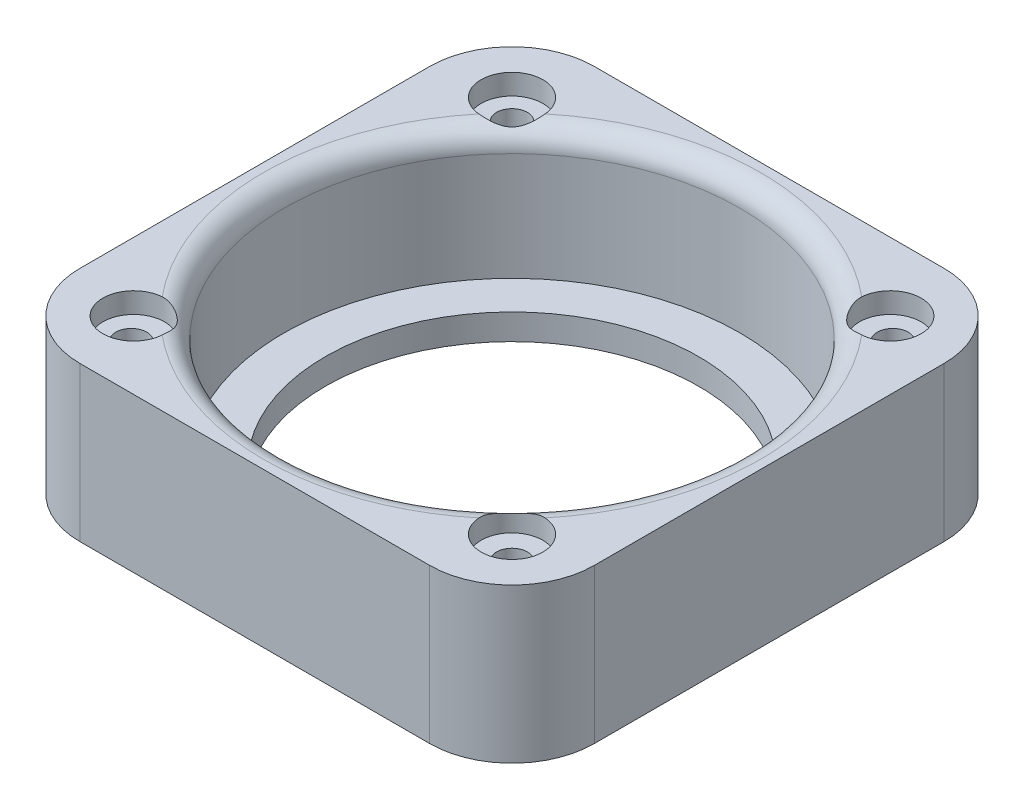
SolidWorks part; units mm, degrees
ref_plane "前视基准面" through (0, 0, 0) normal (0, 0, 1) x (1, 0, 0)
ref_plane "上视基准面" through (0, 0, 0) normal (0, 1, 0) x (1, 0, 0)
ref_plane "右视基准面" through (0, 0, 0) normal (1, 0, 0) x (0, 0, -1)
sketch "草图1" plane through (0, 0, 0) normal (0, 1, 0) x (1, 0, 0)
  circle A0 centre (0, 0) radius 25
extrude "凸台-拉伸1" add sketch "草图1" along normal blind 15
sketch "草图2" plane through (0, 15, 0) normal (0, 1, 0) x (1, 0, 0)
  circle A0 centre (0, 0) radius 22.15
  dimension "D1" = 44.3
extrude "切除-拉伸1" cut sketch "草图2" against normal blind 12.5
sketch "草图3" plane through (0, 2.5, 0) normal (0, 1, 0) x (1, 0, 0)
  circle A0 centre (0, 0) radius 18.15
  circle A1 centre (0, 0) radius 22.15 construction
  dimension "D1" = 4
extrude "切除-拉伸2" cut sketch "草图3" against normal blind 12.5
sketch "草图4" plane through (0, 0, 0) normal (0, 1, 0) x (1, 0, 0)
  line L1 (-25, 25) -> (25, 25)
  line L2 (-25, 25) -> (-25, -25)
  line L3 (-25, -25) -> (25, -25)
  line L4 (25, 25) -> (25, -25)
  line L5 (-25, 25) -> (25, -25) construction
  line L6 (-25, -25) -> (25, 25) construction
  circle A0 centre (0, 0) radius 25
  circle A1 centre (-18.3848, 18.3848) radius 1.5
  circle A2 centre (18.6152, 18.3848) radius 1.5
  circle A3 centre (18.6152, -18.6152) radius 1.5
  circle A4 centre (-18.3848, -18.6152) radius 1.5
  point P0 (0, 0)
  point P20 (0.1152, -0.1152)
  dimension "D3" = 3
  dimension "D4" = 26
  dimension "D6" = 37
  dimension "D7" = 37
  dimension "D1" = 50
  dimension "D2" = 50
  dimension "D5" = 4
extrude "凸台-拉伸2" add sketch "草图4" along normal blind 15 contours A0 L1 L2 | A0 L4 L1 | A0 L2 L3 | A0 L3 L4 region at (-19.4617, 0, -19.4617) region at (12.5, 0, -24.6464) region at (-23.5702, 0, 9.3406) region at (24.6464, 0, 12.5)
fillet "圆角1" radius 8 4 edges at (-25, 7.5, 25) (25, 7.5, 25) (25, 7.5, -25) (-25, 7.5, -25)
sketch "草图5" plane through (0, 15, 0) normal (0, 1, 0) x (1, 0, 0)
  circle A0 centre (-18.3848, 18.3848) radius 1.5
  circle A1 centre (18.6152, 18.3848) radius 1.5
  circle A2 centre (18.6152, -18.6152) radius 1.5
  circle A3 centre (-18.3848, -18.6152) radius 1.5
  point P12 (0.1152, -0.1152)
  dimension "D1" = 4
extrude "切除-拉伸3" cut sketch "草图5" against normal blind 15
sketch "草图6" plane through (0, 15, 0) normal (0, 1, 0) x (1, 0, 0)
  circle A0 centre (-18.3848, 18.3848) radius 3
  dimension "D1" = 6
extrude "切除-拉伸4" cut sketch "草图6" against normal blind 2
pattern_circular "阵列(圆周)1" count 4 over 360 about axis through (0, -10, 0) along (0, 1, 0) of "切除-拉伸4"
sketch "草图9" plane through (0, 15, 0) normal (0, 1, 0) x (1, 0, 0)
  circle A0 centre (0, 0) radius 22.75 construction
  circle A1 centre (-22.75, 0) radius 1
  circle A2 centre (22.75, 0) radius 1
  dimension "D1" = 45.5
fillet "圆角2" radius 2 1 edges at (0, 15, 22.15)
